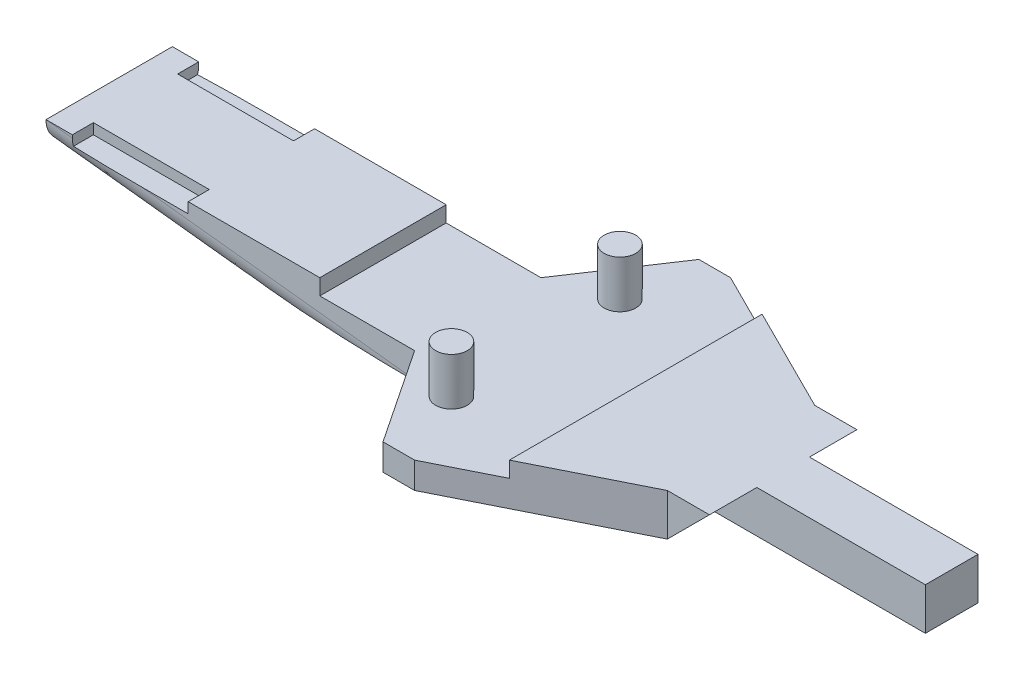
SolidWorks part; units mm, degrees
ref_plane "Front Plane" through (0, 0, 0) normal (0, 0, 1) x (1, 0, 0)
ref_plane "Top Plane" through (0, 0, 0) normal (0, 1, 0) x (1, 0, 0)
ref_plane "Right Plane" through (0, 0, 0) normal (1, 0, 0) x (0, 0, -1)
sketch "Sketch1" plane through (0, 0, 0) normal (0, 1, 0) x (1, 0, 0)
  line L0 (-1, 15) -> (2, 15)
  line L1 (0, 0) -> (1879.8507, 0) construction
  line L2 (2, 15) -> (18, 7)
  line L3 (18, 7) -> (23, 7)
  line L4 (23, 7) -> (23, -7)
  line L5 (-1, 15) -> (-7, 6)
  line L6 (-7, 6) -> (-42, 6)
  line L7 (-42, 6) -> (-42, -6)
  line L8 (-7, -6) -> (-42, -6)
  line L9 (-1, -15) -> (-7, -6)
  line L10 (18, -7) -> (23, -7)
  line L11 (2, -15) -> (18, -7)
  line L12 (-1, -15) -> (2, -15)
  line L13 (-39.5, 6) -> (-39.5, 9)
  line L14 (-39.5, 9) -> (-42, 11.5)
  line L15 (-42, 11.5) -> (-42, 20.5)
  line L16 (-42, 20.5) -> (-39, 20.5)
  line L17 (-39, 20.5) -> (-28.5, 9)
  line L18 (-28.5, 9) -> (-28.5, 6)
  line L19 (-28.5, -9) -> (-28.5, -6)
  line L20 (-39, -20.5) -> (-28.5, -9)
  line L21 (-42, -20.5) -> (-39, -20.5)
  line L22 (-42, -11.5) -> (-42, -20.5)
  line L23 (-39.5, -9) -> (-42, -11.5)
  line L24 (-39.5, -6) -> (-39.5, -9)
  line L25 (2, 15) -> (5.0407, 13.4797)
  line L26 (5.0407, 13.4797) -> (-37.7143, 34.8571)
  line L27 (-18.2143, 6) -> (-37.7143, 27.3571)
  line L28 (-37.7143, 27.3571) -> (-37.7143, 34.8571)
  point P12 (-42, 0)
  point P15 (23, 0)
  dimension "D1" = 3
  dimension "D2" = 1
  dimension "D3" = 15
  dimension "D4" = 18
  dimension "D5" = 7
  dimension "D6" = 5
  dimension "D7" = 6
  dimension "D8" = 6
  dimension "D9" = 35
  dimension "D10" = 3
  dimension "D11" = 5.5
  dimension "D12" = 9
  dimension "D13" = 3
  dimension "D14" = 10.5
  dimension "D15" = 3
  dimension "D16" = 11
  dimension "D17" = 2.5
  dimension "D18" = 19.5
  dimension "D19" = 7.5
extrude "Boss-Extrude1" add sketch "Sketch1" along normal blind 4 contours L7 L1 L4 L3 L2 L0 L5 L6 | L1 L7 L8 L9 L12 L11 L10 L4 region at (-5.748, 0, 0)
sketch "Sketch2" plane through (0, 4, 0) normal (0, 1, 0) x (1, 0, 0)
  line L0 (0, 0) -> (-13.3344, 0) construction
  circle A0 centre (-1.5, 8) radius 1.5
  circle A1 centre (-1.5, -8) radius 1.5
  dimension "D1" = 3
  dimension "D2" = 8
  dimension "D3" = 1.5
extrude "Boss-Extrude2" add sketch "Sketch2" along normal blind 3
sketch "Sketch3" plane through (0, 0, 6) normal (0, 0, 1) x (1, 0, 0)
  line L0 (-24, 0) -> (-42, 2)
  line L1 (-7, 0) -> (-42, 0) construction
  line L2 (-42, 4) -> (-42, 0) construction
  line L3 (-42, 2) -> (-42, 0)
  line L4 (-42, 0) -> (-24, 0)
  dimension "D1" = 2
  dimension "D2" = 18
extrude "Cut-Extrude1" cut sketch "Sketch3" against normal blind 13
sketch "Sketch4" plane through (-42, 0, 0) normal (-1, 0, 0) x (0, 0, 1)
  line L0 (-6, 4) -> (6, 4) construction
  line L1 (6, 4) -> (6, 0) construction
  line L2 (-6, 4) -> (-6, 2) construction
  line L3 (-6, 4) -> (-6, 0)
  line L4 (-6, 0) -> (6, 0)
  line L5 (6, 0) -> (6, 4)
  line L6 (-1.25, 2.9103) -> (1.25, 2.9103)
  circle A0 centre (3.5, 4) radius 2.5
  circle A1 centre (-3.5, 4) radius 2.5
  line M1 (-6, 4) -> (-6, 2)
  line M2 (-6, 2) -> (6, 2)
  line M3 (6, 2) -> (6, 4)
  dimension "D1" = 5
  dimension "D2" = 5
  dimension "D3" = 2.5
  dimension "D4" = 2.5
  dimension "D5" = 2.5
extrude "Cut-Extrude2" cut sketch "Sketch4" along direction (-0.9939, 0.1104, 0) on the side against the normal blind 49 contours A1 M1 M2 | A1 A0 L6 M2 | A0 M2 M3 region at (-42, 2.4778, -5.7141) region at (-42, 2.4195, 0) region at (-42, 2.4778, 5.7141)
sketch "Sketch5" plane through (0, 0, 15) normal (0, 0, 1) x (1, 0, 0)
  line L1 (-7, 4) -> (8, 4)
  line L3 (-7, 2.5) -> (8, 2.5)
  line L5 (8, 4) -> (8, 2.5)
  line L6 (-7, 4) -> (-16, 4)
  line L8 (-7, 2.5) -> (-16, 2.5)
  line L9 (-16, 4) -> (-16, 2.5)
  dimension "D1" = 1.5
  dimension "D2" = 9
extrude "Cut-Extrude3" cut sketch "Sketch5" against normal blind 37
sketch "Sketch6" plane through (0, 7, 0) normal (0, 1, 0) x (1, 0, 0)
  circle A0 centre (-1.5, -8) radius 1.5
  circle A1 centre (-1.5, 8) radius 1.5
  circle A2 centre (-1.5, 8) radius 1.5 construction
  circle A3 centre (-1.5, -8) radius 1.5 construction
extrude "Boss-Extrude3" add sketch "Sketch6" against normal blind 5
sketch "Sketch7" plane through (0, 0, 6) normal (0, 0, 1) x (1, 0, 0)
  line L0 (-16, 4) -> (-42, 4) construction
  line L1 (-39.5, 4) -> (-28.5, 4)
  line L2 (-39.5, 4) -> (-39.5, 3)
  line L3 (-39.5, 3) -> (-28.5, 3)
  line L4 (-28.5, 4) -> (-28.5, 3)
  line L5 (-42, 4) -> (-42, 2) construction
  dimension "D1" = 11
  dimension "D2" = 2.5
  dimension "D3" = 1
extrude "Cut-Extrude4" cut sketch "Sketch7" against normal blind 2
extrude "Cut-Extrude5" cut sketch "Sketch7<2>" along normal blind 2 from surface starting at face at (-17.6, 2.6222, -6)
sketch "Sketch7<2>" plane through (0, 0, 6) normal (0, 0, 1) x (1, 0, 0) same geometry as "Sketch7"
sketch "Sketch8" plane through (23, 0, 0) normal (1, 0, 0) x (0, 0, -1)
  line L1 (-7, 4) -> (7, 4)
  line L2 (-7, 4) -> (-7, 0)
  line L3 (-7, 0) -> (7, 0)
  line L4 (7, 4) -> (7, 0)
extrude "Boss-Extrude4" add sketch "Sketch8" along normal blind 3
sketch "Sketch9" plane through (26, 0, 0) normal (1, 0, 0) x (0, 0, -1)
  line L0 (7, 4) -> (-7, 4) construction
  line L1 (-2.5, 4) -> (2.5, 4)
  line L2 (-2.5, 4) -> (-2.5, 0)
  line L3 (-2.5, 0) -> (2.5, 0)
  line L4 (2.5, 4) -> (2.5, 0)
  line L5 (-7, 0) -> (7, 0) construction
  line L6 (-7, 4) -> (-7, 0) construction
  dimension "D1" = 4.5
  dimension "D2" = 5
extrude "Boss-Extrude5" add sketch "Sketch9" along normal blind 12
sketch "Sketch10" plane through (0, 0, 7) normal (0, 0, 1) x (1, 0, 0)
  line L0 (18, 0) -> (22, 4)
  line L1 (18, 4) -> (26, 4) construction
  line L2 (22, 4) -> (26, 4)
  line L3 (26, 4) -> (26, 0)
  line L4 (26, 0) -> (18, 0)
  dimension "D1" = 4
extrude "Cut-Extrude6" cut sketch "Sketch10" against normal blind 4.5
extrude "Cut-Extrude7" cut sketch "Sketch10<3>" along normal blind 4.5 from surface starting at face at (22, 2, -7)
sketch "Sketch10<3>" plane through (0, 0, 7) normal (0, 0, 1) x (1, 0, 0) same geometry as "Sketch10"
